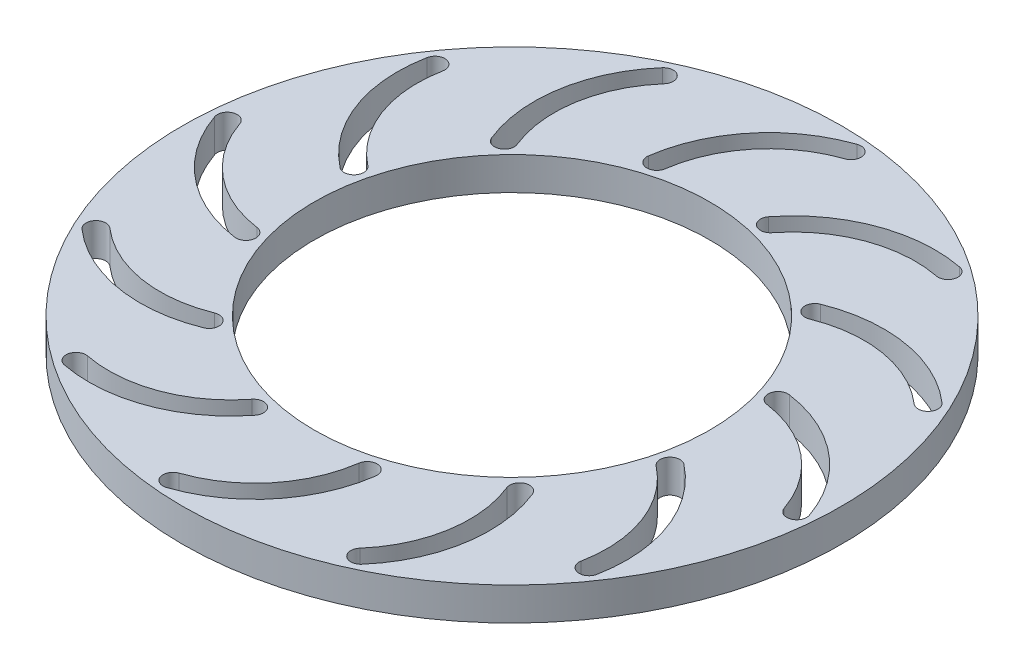
SolidWorks part; units mm, degrees
note: The reader was unsure of these and kept them because the rebuilt part matched: shared geometry of "Sketch1<4>", "Sketch1<6>", "Sketch1<7>".
ref_plane "Front Plane" through (0, 0, 0) normal (0, 0, 1) x (1, 0, 0)
ref_plane "Top Plane" through (0, 0, 0) normal (0, 1, 0) x (1, 0, 0)
ref_plane "Right Plane" through (0, 0, 0) normal (1, 0, 0) x (0, 0, -1)
sketch "Sketch1" plane through (0, 0, 0) normal (0, 1, 0) x (1, 0, 0)
  circle A0 centre (0, 0) radius 3
  circle A1 centre (0, 0) radius 5
  circle A2 centre (0, 0) radius 3.25
  circle A3 centre (0, 0) radius 4.75
  arc A4 (0.7617, 3.1595) -> (2.7232, 3.8919) centre (2.3385, 1.9292) cw construction
  arc A5 (2.752, 4.0391) -> (0.6434, 3.2518) centre (2.3385, 1.9292) ccw
  arc A6 (2.6943, 3.7447) -> (0.8799, 3.0672) centre (2.3385, 1.9292) ccw
  arc A7 (2.6943, 3.7447) -> (2.752, 4.0391) centre (2.7232, 3.8919) ccw
  arc A8 (0.6434, 3.2518) -> (0.8799, 3.0672) centre (0.7617, 3.1595) ccw
  arc A9 (4.2057, 1.8958) -> (2.2956, 2.2163) centre (2.9898, 0.5015) ccw
  arc A10 (4.2057, 1.8958) -> (4.4029, 2.1219) centre (4.3043, 2.0089) ccw
  arc A11 (2.1831, 2.4944) -> (2.2956, 2.2163) centre (2.2394, 2.3554) ccw
  arc A12 (4.4029, 2.1219) -> (2.1831, 2.4944) centre (2.9898, 0.5015) ccw
  arc A13 (2.2394, 2.3554) -> (4.3043, 2.0089) centre (2.9898, 0.5015) cw construction
  arc A14 (4.5902, -0.461) -> (3.0963, 0.7716) centre (2.84, -1.0606) ccw
  arc A15 (4.5902, -0.461) -> (4.874, -0.3638) centre (4.7321, -0.4124) ccw
  arc A16 (3.1378, 1.0687) -> (3.0963, 0.7716) centre (3.117, 0.9201) ccw
  arc A17 (4.874, -0.3638) -> (3.1378, 1.0687) centre (2.84, -1.0606) ccw
  arc A18 (3.117, 0.9201) -> (4.7321, -0.4124) centre (2.84, -1.0606) cw construction
  arc A19 (3.7447, -2.6943) -> (3.0672, -0.8799) centre (1.9292, -2.3385) ccw
  arc A20 (3.7447, -2.6943) -> (4.0391, -2.752) centre (3.8919, -2.7232) ccw
  arc A21 (3.2518, -0.6434) -> (3.0672, -0.8799) centre (3.1595, -0.7617) ccw
  arc A22 (4.0391, -2.752) -> (3.2518, -0.6434) centre (1.9292, -2.3385) ccw
  arc A23 (3.1595, -0.7617) -> (3.8919, -2.7232) centre (1.9292, -2.3385) cw construction
  arc A24 (1.8958, -4.2057) -> (2.2163, -2.2956) centre (0.5015, -2.9898) ccw
  arc A25 (1.8958, -4.2057) -> (2.1219, -4.4029) centre (2.0089, -4.3043) ccw
  arc A26 (2.4944, -2.1831) -> (2.2163, -2.2956) centre (2.3554, -2.2394) ccw
  arc A27 (2.1219, -4.4029) -> (2.4944, -2.1831) centre (0.5015, -2.9898) ccw
  arc A28 (2.3554, -2.2394) -> (2.0089, -4.3043) centre (0.5015, -2.9898) cw construction
  arc A29 (-0.461, -4.5902) -> (0.7716, -3.0963) centre (-1.0606, -2.84) ccw
  arc A30 (-0.461, -4.5902) -> (-0.3638, -4.874) centre (-0.4124, -4.7321) ccw
  arc A31 (1.0687, -3.1378) -> (0.7716, -3.0963) centre (0.9201, -3.117) ccw
  arc A32 (-0.3638, -4.874) -> (1.0687, -3.1378) centre (-1.0606, -2.84) ccw
  arc A33 (0.9201, -3.117) -> (-0.4124, -4.7321) centre (-1.0606, -2.84) cw construction
  arc A34 (-2.6943, -3.7447) -> (-0.8799, -3.0672) centre (-2.3385, -1.9292) ccw
  arc A35 (-2.6943, -3.7447) -> (-2.752, -4.0391) centre (-2.7232, -3.8919) ccw
  arc A36 (-0.6434, -3.2518) -> (-0.8799, -3.0672) centre (-0.7617, -3.1595) ccw
  arc A37 (-2.752, -4.0391) -> (-0.6434, -3.2518) centre (-2.3385, -1.9292) ccw
  arc A38 (-0.7617, -3.1595) -> (-2.7232, -3.8919) centre (-2.3385, -1.9292) cw construction
  arc A39 (-4.2057, -1.8958) -> (-2.2956, -2.2163) centre (-2.9898, -0.5015) ccw
  arc A40 (-4.2057, -1.8958) -> (-4.4029, -2.1219) centre (-4.3043, -2.0089) ccw
  arc A41 (-2.1831, -2.4944) -> (-2.2956, -2.2163) centre (-2.2394, -2.3554) ccw
  arc A42 (-4.4029, -2.1219) -> (-2.1831, -2.4944) centre (-2.9898, -0.5015) ccw
  arc A43 (-2.2394, -2.3554) -> (-4.3043, -2.0089) centre (-2.9898, -0.5015) cw construction
  arc A44 (-4.5902, 0.461) -> (-3.0963, -0.7716) centre (-2.84, 1.0606) ccw
  arc A45 (-4.5902, 0.461) -> (-4.874, 0.3638) centre (-4.7321, 0.4124) ccw
  arc A46 (-3.1378, -1.0687) -> (-3.0963, -0.7716) centre (-3.117, -0.9201) ccw
  arc A47 (-4.874, 0.3638) -> (-3.1378, -1.0687) centre (-2.84, 1.0606) ccw
  arc A48 (-3.117, -0.9201) -> (-4.7321, 0.4124) centre (-2.84, 1.0606) cw construction
  arc A49 (-3.7447, 2.6943) -> (-3.0672, 0.8799) centre (-1.9292, 2.3385) ccw
  arc A50 (-3.7447, 2.6943) -> (-4.0391, 2.752) centre (-3.8919, 2.7232) ccw
  arc A51 (-3.2518, 0.6434) -> (-3.0672, 0.8799) centre (-3.1595, 0.7617) ccw
  arc A52 (-4.0391, 2.752) -> (-3.2518, 0.6434) centre (-1.9292, 2.3385) ccw
  arc A53 (-3.1595, 0.7617) -> (-3.8919, 2.7232) centre (-1.9292, 2.3385) cw construction
  arc A54 (-1.8958, 4.2057) -> (-2.2163, 2.2956) centre (-0.5015, 2.9898) ccw
  arc A55 (-1.8958, 4.2057) -> (-2.1219, 4.4029) centre (-2.0089, 4.3043) ccw
  arc A56 (-2.4944, 2.1831) -> (-2.2163, 2.2956) centre (-2.3554, 2.2394) ccw
  arc A57 (-2.1219, 4.4029) -> (-2.4944, 2.1831) centre (-0.5015, 2.9898) ccw
  arc A58 (-2.3554, 2.2394) -> (-2.0089, 4.3043) centre (-0.5015, 2.9898) cw construction
  arc A59 (0.461, 4.5902) -> (-0.7716, 3.0963) centre (1.0606, 2.84) ccw
  arc A60 (0.461, 4.5902) -> (0.3638, 4.874) centre (0.4124, 4.7321) ccw
  arc A61 (-1.0687, 3.1378) -> (-0.7716, 3.0963) centre (-0.9201, 3.117) ccw
  arc A62 (0.3638, 4.874) -> (-1.0687, 3.1378) centre (1.0606, 2.84) ccw
  arc A63 (-0.9201, 3.117) -> (0.4124, 4.7321) centre (1.0606, 2.84) cw construction
  point P6 (1.6389, 3.8029)
  point P14 (3.3208, 2.4739)
  point P24 (4.1129, 0.4821)
  point P32 (3.8029, -1.6389)
  point P40 (2.4739, -3.3208)
  point P48 (0.4821, -4.1129)
  point P56 (-1.6389, -3.8029)
  point P64 (-3.3208, -2.4739)
  point P72 (-4.1129, -0.4821)
  point P80 (-3.8029, 1.6389)
  point P88 (-2.4739, 3.3208)
  point P96 (-0.4821, 4.1129)
  point P104 (0, 0)
  dimension "D1" = 6
  dimension "D2" = 0.25
  dimension "1" = 10
  dimension "D3" = 0.25
  dimension "D4" = 2
  dimension "D6" = 12
extrude "Boss-Extrude1" add sketch "Sketch1" along normal blind 0.5 contours A1 | A0
extrude "Cut-Extrude2" cut sketch "Sketch1<4>" along normal blind 0.5 contours A49 A51 A52 A50
sketch "Sketch1<4>" plane through (0, 0, 0) normal (0, 1, 0) x (1, 0, 0) same geometry as "Sketch1"
extrude "Cut-Extrude3" cut sketch "Sketch1<6>" along normal blind 0.5 contours A54 A56 A57 A55 | A59 A61 A62 A60 | A6 A8 A5 A7
sketch "Sketch1<6>" plane through (0, 0, 0) normal (0, 1, 0) x (1, 0, 0) same geometry as "Sketch1"
extrude "Cut-Extrude5" cut sketch "Sketch1<7>" along normal blind 0.5 contours A12 A11 A9 A10 | A17 A16 A14 A15 | A22 A21 A19 A20 | A27 A26 A24 A25 | A32 A31 A29 A30 | A34 A36 A37 A35 | A39 A41 A42 A40 | A44 A46 A47 A45
sketch "Sketch1<7>" plane through (0, 0, 0) normal (0, 1, 0) x (1, 0, 0) same geometry as "Sketch1"
